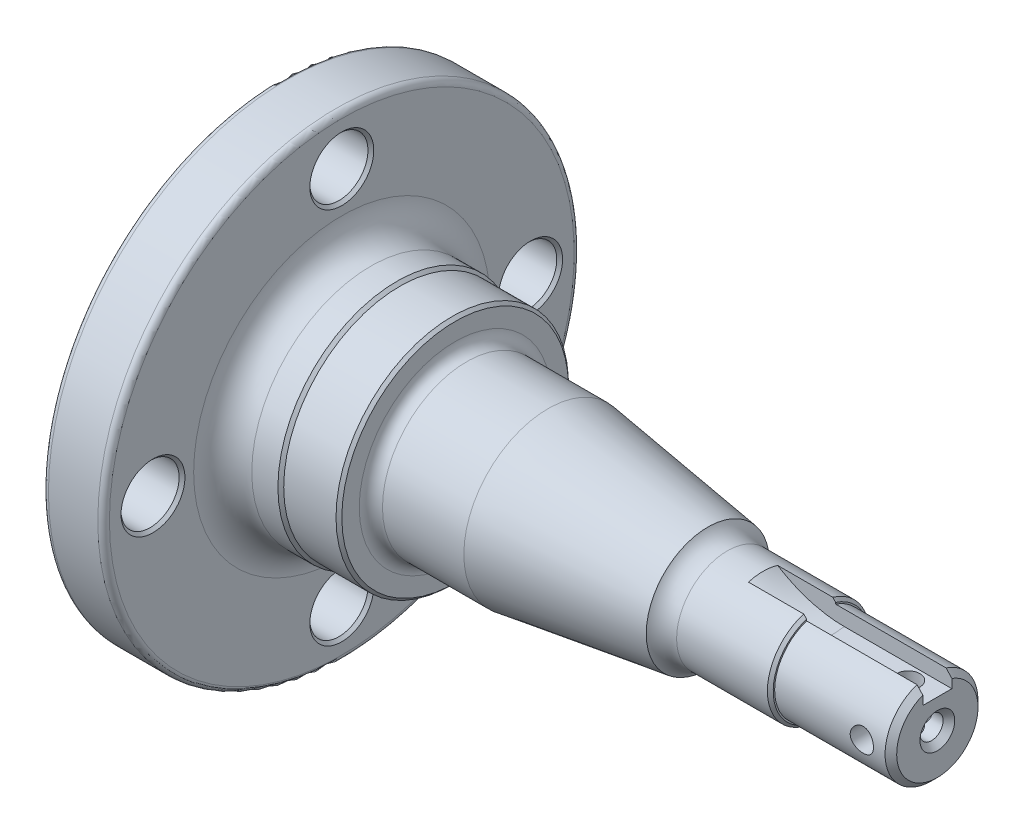
SolidWorks part; units mm, degrees
ref_plane "Plano frontal" through (0, 0, 0) normal (0, 0, 1) x (1, 0, 0)
ref_plane "Plano superior" through (0, 0, 0) normal (0, 1, 0) x (1, 0, 0)
ref_plane "Plano direito" through (0, 0, 0) normal (1, 0, 0) x (0, 0, -1)
sketch "Esboço1" plane through (0, 0, 0) normal (0, 0, 1) x (1, 0, 0)
  line L0 (-46.4595, 0) -> (66.5405, 0) construction
  line L1 (-46.4595, 0) -> (-46.4595, 41)
  line L2 (-46.4595, 41) -> (-35.9595, 41)
  line L3 (-35.9595, 41) -> (-35.9595, 20.5)
  line L4 (-35.9595, 20.5) -> (-26.4595, 20.5)
  line L5 (-26.4595, 20.5) -> (-26.4595, 20)
  line L6 (-26.4595, 20) -> (-16.4595, 20)
  line L7 (-16.4595, 20) -> (-16.4595, 14.5)
  line L8 (-16.4595, 14.5) -> (-0.4595, 14.5)
  line L9 (-0.4595, 14.5) -> (27.0405, 10.6)
  line L10 (27.0405, 10.6) -> (27.0405, 8.75)
  line L11 (27.0405, 8.75) -> (46.5405, 8.75)
  line L12 (46.5405, 8.75) -> (46.5405, 8)
  line L13 (46.5405, 8) -> (66.5405, 8)
  line L14 (66.5405, 8) -> (66.5405, 0)
  line L15 (-46.4595, 0) -> (66.5405, 0)
  dimension "D1" = 41
  dimension "D2" = 20.5
  dimension "D3" = 20
  dimension "D4" = 14.5
  dimension "D5" = 10.6
  dimension "D6" = 8.75
  dimension "D7" = 8
  dimension "D8" = 10.5
  dimension "D9" = 20
  dimension "D10" = 30
  dimension "D11" = 46
  dimension "D12" = 73.5
  dimension "D13" = 19.5
  dimension "D14" = 20
revolve "Revolução1" add sketch "Esboço1" angle 360 about L0
sketch "Esboço2" plane through (-46.4595, 0, 0) normal (-1, 0, 0) x (0, 0, 1)
  circle A0 centre (0, 0) radius 20
  dimension "D1" = 40
extrude "Corte-extrusão1" cut sketch "Esboço2" against normal blind 2.8
sketch "Esboço3" plane through (-43.6595, 0, 0) normal (-1, 0, 0) x (0, 0, 1)
  line L1 (-13.85, 7.25) -> (13.85, 7.25)
  line L2 (-13.85, 7.25) -> (-13.85, -7.25)
  line L3 (-13.85, -7.25) -> (13.85, -7.25)
  line L4 (13.85, 7.25) -> (13.85, -7.25)
  line L5 (-13.85, 7.25) -> (13.85, -7.25) construction
  line L6 (-13.85, -7.25) -> (13.85, 7.25) construction
  point P0 (0, 0)
  dimension "D1" = 27.7
  dimension "D2" = 14.5
extrude "Corte-extrusão2" cut sketch "Esboço3" against normal blind 7.5
fillet "Filete1" radius 0.5 13 edges at (-39.9095, -7.25, -13.85) (-39.9095, 7.25, -13.85) (-39.9095, 7.25, 13.85) (-39.9095, -7.25, 13.85) (-36.1595, -7.25, 0) (-36.1595, 0, 13.85) (-36.1595, 7.25, 0) (-43.6595, 0, 13.85) (-36.1595, 0, -13.85) (-43.6595, -7.25, 0) (-43.6595, 0, -13.85) (-43.6595, 7.25, 0) (-43.6595, 0, 20)
sketch "Esboço4" plane through (-46.4595, 0, 0) normal (-1, 0, 0) x (0, 0, 1)
  circle A0 centre (0, 0) radius 32.5 construction
  circle A1 centre (0, 32.5) radius 5
  circle A2 centre (32.5, 0) radius 5
  circle A3 centre (0, -32.5) radius 5
  circle A4 centre (-32.5, 0) radius 5
  point P14 (0, 0)
  dimension "D1" = 65
  dimension "D2" = 10
  dimension "D3" = 4
extrude "Corte-extrusão3" cut sketch "Esboço4" against normal through all
chamfer "Chanfro1" distance 0.5 angle 45 8 edges at (-46.4595, 0, 37.5) (-35.9595, 0, 37.5) (-46.4595, -32.5, 5) (-35.9595, -32.5, 5) (-46.4595, 0, -27.5) (-35.9595, 0, -27.5) (-35.9595, 32.5, 5) (-46.4595, 32.5, 5)
fillet "Filete2" radius 1 2 edges at (-46.4595, 0, 41) (-35.9595, 0, 41)
fillet "Filete3" radius 5 1 edges at (-35.9595, 0, 20.5)
chamfer "Chanfro2" distance 0.5 angle 45 1 edges at (-26.4595, 0, 20)
chamfer "Chanfro3" distance 0.5 angle 45 1 edges at (-16.4595, 0, 20)
fillet "Filete4" radius 2 1 edges at (-16.4595, 0, 14.5)
fillet "Filete5" radius 4 1 edges at (27.0405, 0, 8.75)
chamfer "Chanfro5" distance 0.5 angle 45 1 edges at (46.5405, 0, 8.75)
chamfer "Chanfro6" distance 1.5 angle 45 1 edges at (66.5405, 0, 8)
sketch "Esboço5" plane through (66.5405, 0, 0) normal (1, 0, 0) x (0, 0, -1)
  line L1 (-10.7777, 9.456) -> (10.7777, 9.456)
  line L2 (-10.7777, 9.456) -> (-10.7777, -9.456)
  line L3 (-10.7777, -9.456) -> (10.7777, -9.456)
  line L4 (10.7777, 9.456) -> (10.7777, -9.456)
  line L5 (-10.7777, 9.456) -> (10.7777, -9.456) construction
  line L6 (-10.7777, -9.456) -> (10.7777, 9.456) construction
  point P0 (0, 0)
extrude "Ressalto-extrusão1" add sketch "Esboço5" against normal blind 7.5
sketch "Esboço6" plane through (0, 9.456, 0) normal (0, 1, 0) x (1, 0, 0)
  line L0 (66.5405, 0) -> (61.5405, 0) construction
  line L1 (66.5405, 10.7777) -> (66.5405, -10.7777) construction
  circle A0 centre (61.5405, 0) radius 2
  dimension "D2" = 4
  dimension "D1" = 5
extrude "Corte-extrusão4" cut sketch "Esboço6" against normal blind 18
sketch "Esboço7" plane through (0, 0, 10.7777) normal (0, 0, 1) x (1, 0, 0)
  line L0 (66.5405, 0) -> (61.5405, 0) construction
  line L1 (66.5405, 9.456) -> (66.5405, -9.456) construction
  circle A0 centre (61.5405, 0) radius 2
  dimension "D2" = 4
  dimension "D1" = 5
extrude "Corte-extrusão8" cut sketch "Esboço7" against normal through all
sketch "Esboço8" plane through (66.5405, 0, 0) normal (1, 0, 0) x (0, 0, -1)
  line L1 (-24.4714, 20.2203) -> (24.4714, 20.2203)
  line L2 (-24.4714, 20.2203) -> (-24.4714, -20.2203)
  line L3 (-24.4714, -20.2203) -> (24.4714, -20.2203)
  line L4 (24.4714, 20.2203) -> (24.4714, -20.2203)
  line L5 (-24.4714, 20.2203) -> (24.4714, -20.2203) construction
  line L6 (-24.4714, -20.2203) -> (24.4714, 20.2203) construction
  circle A0 centre (0, 0) radius 8
  dimension "D1" = 16
extrude "Corte-extrusão9" cut sketch "Esboço8" against normal blind 10
sketch "Esboço10" plane through (66.5405, 0, 0) normal (1, 0, 0) x (0, 0, -1)
  line L0 (0, 8) -> (0, 5) construction
  line L1 (-2.5, 5) -> (-2.5, 12.1563)
  line L2 (-2.5, 12.1563) -> (2.5, 12.1563)
  line L3 (-2.5, 5) -> (2.5, 5)
  line L4 (2.5, 12.1563) -> (2.5, 5)
  circle A0 centre (0, 0) radius 8 construction
  dimension "D1" = 3
  dimension "D2" = 2.5
  dimension "D3" = 2.5
extrude "Corte-extrusão10" cut sketch "Esboço10" against normal blind 30
fillet "Filete6" radius 20 1 edges at (36.5405, 5, 0)
chamfer "Chanfro8" distance 1 angle 45 1 edges at (66.5405, -8, 0)
sketch "Esboço11" plane through (66.5405, 0, 0) normal (1, 0, 0) x (0, 0, -1)
  circle A0 centre (0, 0) radius 2
  dimension "D1" = 4
extrude "Corte-extrusão11" cut sketch "Esboço11" against normal blind 5
chamfer "Chanfro9" distance 1 angle 45 1 edges at (66.5405, 0, -2)
